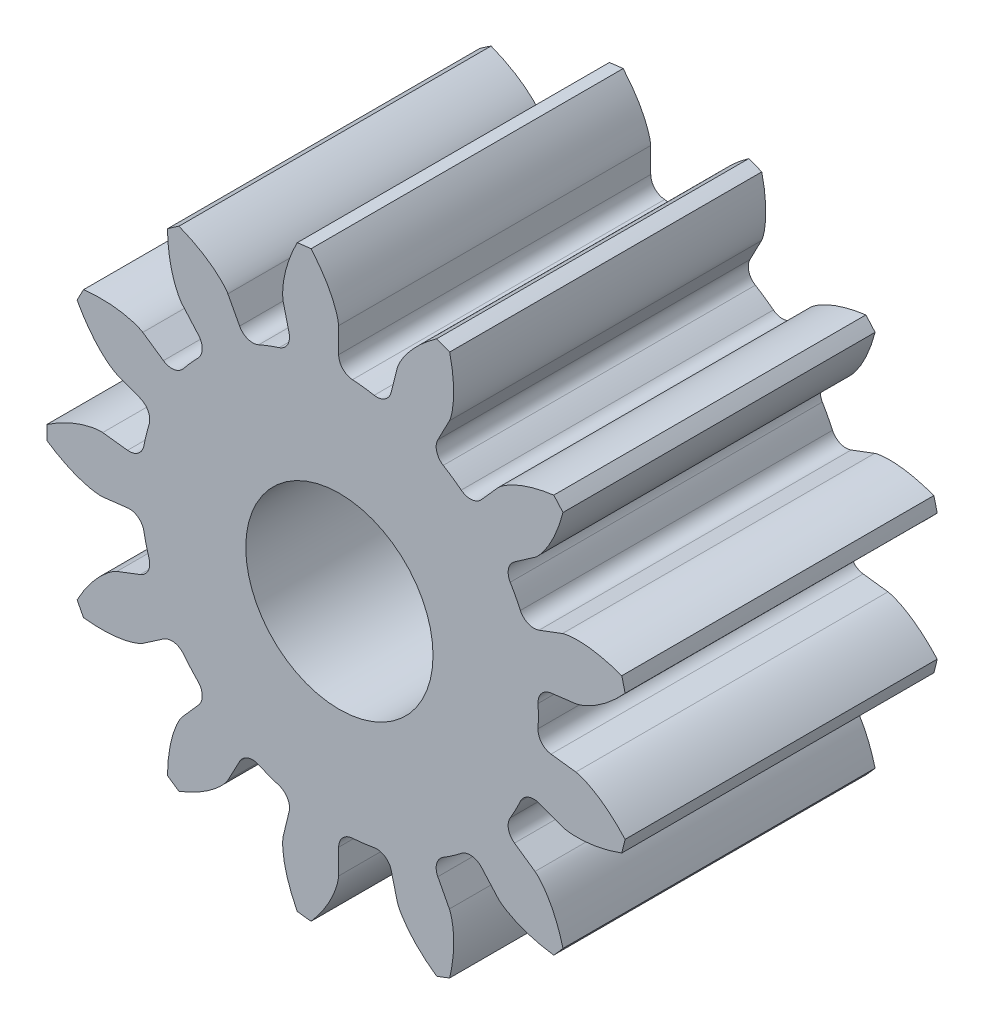
SolidWorks part; units mm, degrees
ref_plane "Front Plane" through (0, 0, 0) normal (0, 0, 1) x (1, 0, 0)
ref_plane "Top Plane" through (0, 0, 0) normal (0, 1, 0) x (1, 0, 0)
ref_plane "Right Plane" through (0, 0, 0) normal (1, 0, 0) x (0, 0, -1)
ref_axis "Gear Axis" through (0, 0, -0.5001) along (0, 0, 1)
sketch "Blank Sketch" plane through (0, 0, 0) normal (0, 0, 1) x (1, 0, 0)
  circle A0 centre (0, 0) radius 9.375
  dimension "OD" = 18.75
extrude "Blank" add sketch "Blank Sketch" along normal blind 10
sketch "Tooth Space Sketch" plane through (0, 0, 0) normal (0, 0, 1) x (1, 0, 0)
  line L0 (7.576, 0.9473) -> (6.7807, 0.8478)
  line L1 (7.576, -0.9473) -> (6.7807, -0.8478)
  line L2 (10.0751, 3.3739) -> (10.0751, -3.3739)
  arc A0 (6.7807, 0.8478) -> (6.3654, 0.3504) centre (6.8396, 0.3765) ccw
  arc A1 (6.3654, -0.3504) -> (6.7807, -0.8478) centre (6.8396, -0.3765) ccw
  arc A2 (6.3654, -0.3504) -> (6.3654, 0.3504) centre (0, 0) ccw
  spline S0 degree 4 poles (7.576, 0.9473) (7.5812, 0.948) (7.5959, 0.9505) (7.6233, 0.9565) (7.6676, 0.9681) (7.7235, 0.9855) (7.7948, 1.0111) (7.8775, 1.0451) (7.967, 1.0865) (8.0626, 1.1358) (8.1563, 1.1887) (8.2482, 1.2449) (8.3382, 1.3039) (8.4453, 1.3788) (8.5709, 1.4736) (8.7135, 1.5912) (8.87, 1.7325) (9.0235, 1.8847) (9.1695, 2.0411) (9.3109, 2.2064) (9.4434, 2.3715) (9.5743, 2.55) (9.6917, 2.7184) (9.8156, 2.9144) (9.9133, 3.0748) (10.0337, 3.2937) (10.1023, 3.4252) (10.1795, 3.5815) (10.2122, 3.6521) (10.2324, 3.6956) knots 0 0 0 0 0 0.005377 0.015084 0.028532 0.04661 0.064855 0.092111 0.119476 0.146842 0.174209 0.201575 0.228941 0.256307 0.307035 0.361767 0.4165 0.471232 0.525964 0.580697 0.635429 0.690161 0.744894 0.799626 0.854358 0.909091 0.954545 1 1 1 1 1 construction
  spline S1 degree 4 poles (7.576, 0.9473) (7.5812, 0.948) (7.5959, 0.9505) (7.6233, 0.9565) (7.6676, 0.9681) (7.7235, 0.9855) (7.7948, 1.0111) (7.8775, 1.0451) (7.967, 1.0865) (8.0626, 1.1358) (8.1563, 1.1887) (8.2482, 1.2449) (8.3382, 1.3039) (8.4453, 1.3788) (8.5709, 1.4736) (8.7135, 1.5912) (8.87, 1.7325) (9.0235, 1.8847) (9.1695, 2.0411) (9.3109, 2.2064) (9.4434, 2.3715) (9.5743, 2.55) (9.6917, 2.7184) (9.8156, 2.9144) (9.9133, 3.0748) (10.0076, 3.2462) (10.0525, 3.3305) (10.0751, 3.3739) knots 0 0 0 0 0 0.005377 0.015084 0.028532 0.04661 0.064855 0.092111 0.119476 0.146842 0.174209 0.201575 0.228941 0.256307 0.307035 0.361767 0.4165 0.471232 0.525964 0.580697 0.635429 0.690161 0.744894 0.799626 0.854358 0.909091 0.909091 0.909091 0.909091 0.909091
  spline S2 degree 4 poles (7.576, -0.9473) (7.5812, -0.948) (7.5959, -0.9505) (7.6233, -0.9565) (7.6676, -0.9681) (7.7235, -0.9855) (7.7948, -1.0111) (7.8775, -1.0451) (7.967, -1.0865) (8.0626, -1.1358) (8.1563, -1.1887) (8.2482, -1.2449) (8.3382, -1.3039) (8.4453, -1.3788) (8.5709, -1.4736) (8.7135, -1.5912) (8.87, -1.7325) (9.0235, -1.8847) (9.1695, -2.0411) (9.3109, -2.2064) (9.4434, -2.3715) (9.5743, -2.55) (9.6917, -2.7184) (9.8156, -2.9144) (9.9133, -3.0748) (10.0337, -3.2937) (10.1023, -3.4252) (10.1795, -3.5815) (10.2122, -3.6521) (10.2324, -3.6956) knots 0 0 0 0 0 0.005377 0.015084 0.028532 0.04661 0.064855 0.092111 0.119476 0.146842 0.174209 0.201575 0.228941 0.256307 0.307035 0.361767 0.4165 0.471232 0.525964 0.580697 0.635429 0.690161 0.744894 0.799626 0.854358 0.909091 0.954545 1 1 1 1 1 construction
  spline S3 degree 4 poles (7.576, -0.9473) (7.5812, -0.948) (7.5959, -0.9505) (7.6233, -0.9565) (7.6676, -0.9681) (7.7235, -0.9855) (7.7948, -1.0111) (7.8775, -1.0451) (7.967, -1.0865) (8.0626, -1.1358) (8.1563, -1.1887) (8.2482, -1.2449) (8.3382, -1.3039) (8.4453, -1.3788) (8.5709, -1.4736) (8.7135, -1.5912) (8.87, -1.7325) (9.0235, -1.8847) (9.1695, -2.0411) (9.3109, -2.2064) (9.4434, -2.3715) (9.5743, -2.55) (9.6917, -2.7184) (9.8156, -2.9144) (9.9133, -3.0748) (10.0076, -3.2462) (10.0525, -3.3305) (10.0751, -3.3739) knots 0 0 0 0 0 0.005377 0.015084 0.028532 0.04661 0.064855 0.092111 0.119476 0.146842 0.174209 0.201575 0.228941 0.256307 0.307035 0.361767 0.4165 0.471232 0.525964 0.580697 0.635429 0.690161 0.744894 0.799626 0.854358 0.909091 0.909091 0.909091 0.909091 0.909091
  dimension "Root" = 6.375
  dimension "Fillet" = 0.475
extrude "Tooth Space" cut sketch "Tooth Space Sketch" against normal through all both and the other way through all both
pattern_circular "Teeth" count 13 over 360 about axis through (0, 0, -0.5001) along (0, 0, 1) of "Tooth Space"
sketch "Sketch1" plane through (0, 0, 0) normal (0, 0, -1) x (-1, 0, 0)
  circle A0 centre (0, 0) radius 3
  dimension "D1" = 6
extrude "Cut-Extrude1" cut sketch "Sketch1" against normal blind 10
equation "\"No. of Teeth\"= 13"
equation "\"Module\"= 1.25"
equation "\"Bore Diameter\"= 0"
equation "\"Pressure Angle\"= 20"
equation "\"Outer Diameter\"= ( \"No. of Teeth\" + 2 ) * \"Module\""
equation "\"Pitch Diameter\"= \"No. of Teeth\" * \"Module\""
equation "\"Backlash\"= IIF ( \"Module\" <= 1 , 0.3 * \"Module\" , 0.3 )"
equation "\"Arc Length\"= ( ( \"Module\" * pi ) / 2 + \"Backlash\" )"
equation "\"Fillet Radius\"= 0.38 * \"Module\""
equation "\"Tooth Depth\"= IIF ( \"Module\" <= 1.25 , \"Module\" * 2.4 , \"Module\" * 2.25 )"
equation "\"Face Width\"= 10"
equation "\"Root Diameter\"= \"Outer Diameter\" - 2 * \"Tooth Depth\""
equation "\"Base Diameter\"= \"Pitch Diameter\" * cos ( \"Pressure Angle\" )"
equation "\"Base Radius\"= \"Base Diameter\" / 2"
equation "\"Tooth Thickness\"= \"Module\" * pi - \"Arc Length\""
equation "\"Half Space Angle\"= ( \"Arc Length\" / \"Pitch Diameter\" ) * 180 / pi"
equation "\"Involute Fn\"= tan ( \"Pressure Angle\" ) - \"Pressure Angle\" * pi / 180"
equation "\"Flank Offset\"= \"Arc Length\" / \"Pitch Diameter\" - \"Involute Fn\""
equation "\"Tip Cap Diameter\"= \"Outer Diameter\" + 2 * \"Module\""
equation "\"Flank Start Diameter\"= IIF ( \"Base Diameter\" >= ( \"Root Diameter\" + 3 * \"Fillet Radius\" ) , \"Base Diameter\" , \"Root Diameter\" + 3 * \"Fillet Radius\" )"
equation "\"Involute t1\"= ( abs ( ( \"Flank Start Diameter\" / \"Base Diameter\" ) ^ 2 - 1 ) ) ^ 0.5"
equation "\"Involute t2\"= ( abs ( ( \"Tip Cap Diameter\" / \"Base Diameter\" ) ^ 2 - 1 ) ) ^ 0.5"
equation "\"Flank Arc Radius\"= ( \"Pitch Diameter\" / 2 ) * sin ( \"Pressure Angle\" )"
equation "\"Flank Centre Angle\"= \"Half Space Angle\" + \"Pressure Angle\""
equation "\"OD@Blank Sketch\"= \"Outer Diameter\""
equation "\"Width@Blank\"= \"Face Width\""
equation "\"Root@Tooth Space Sketch\"= \"Root Diameter\" / 2"
equation "\"Fillet@Tooth Space Sketch\"= \"Fillet Radius\""
equation "\"Count@Teeth\"= \"No. of Teeth\""
